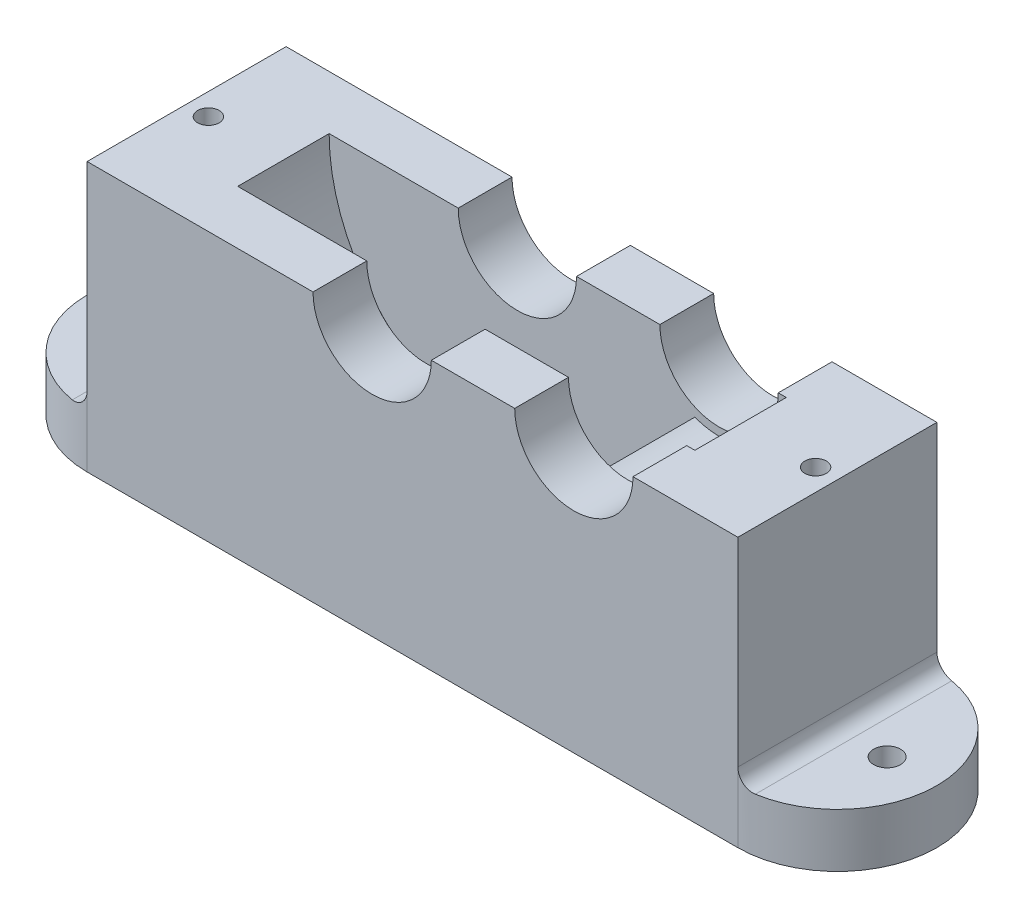
SolidWorks part; units mm, degrees
ref_plane "Front Plane" through (0, 0, 0) normal (0, 0, 1) x (1, 0, 0)
ref_plane "Top Plane" through (0, 0, 0) normal (0, 1, 0) x (1, 0, 0)
ref_plane "Right Plane" through (0, 0, 0) normal (1, 0, 0) x (0, 0, -1)
sketch "Sketch1" plane through (0, 0, 0) normal (0, 0, 1) x (1, 0, 0)
  line L0 (-18.75, 0) -> (18.75, 0)
  line L1 (-73.75, -5) -> (-73.75, -55)
  line L3 (-73.75, -5) -> (-73.75, 5)
  line L4 (-73.75, 5) -> (-63.4714, 5)
  line L10 (40.6874, 5) -> (51.25, 5)
  line L11 (51.25, -5) -> (51.25, 5)
  line L14 (51.25, -5) -> (51.25, -55)
  line L15 (51.25, -55) -> (-73.75, -55)
  circle A0 centre (18.75, 0) radius 7.5
  circle A1 centre (-18.75, 0) radius 30
  arc A2 (20.25, 22.4499) -> (20.25, -22.4499) centre (-18.75, 0) ccw
  arc A3 (20.25, -22.4499) -> (20.25, 22.4499) centre (18.75, 0) ccw
  circle A5 centre (18.75, 0) radius 22.5 construction
  circle A6 centre (-18.75, 0) radius 45 construction
  point P4 (0, 0)
  point P7 (-63.75, 0)
  point P10 (31.25, 0)
  point P13 (16.25, 0)
  point P19 (41.25, 0)
  dimension "D1" = 37.5
  dimension "D2" = 60
  dimension "D3" = 15
  dimension "D4" = 15
  dimension "D5" = 15
extrude "Boss-Extrude2" add sketch "Sketch1" along normal blind 27 contours A3 A2 A1 A0 | A1 | A0 region at (-27.6498, 42.6994, 0) region at (18.75, -7.2879, 0) region at (-47.9015, 0, 0)
shell "Shell5" thickness 10 removed face at (-11.25, 0, 0)
sketch "Sketch2" plane through (0, 0, 17) normal (0, 0, -1) x (-1, 0, 0)
  line L0 (-18.75, 0) -> (18.75, 0) construction
  circle A0 centre (-18.75, 0) radius 4
  circle A1 centre (18.75, 0) radius 4
  point P4 (0, 0)
sketch "Sketch4" plane through (0, 0, 0) normal (0, 0, -1) x (-1, 0, 0)
  arc A0 (-20.25, 22.4499) -> (-20.25, -22.4499) centre (-18.75, 0) ccw construction
  arc A1 (-20.25, -22.4499) -> (-20.25, 22.4499) centre (18.75, 0) ccw construction
  arc A4 (-20.25, 22.4499) -> (-20.25, -22.4499) centre (-18.75, 0) ccw
  arc A5 (-20.25, -22.4499) -> (-20.25, 22.4499) centre (18.75, 0) ccw
extrude "Boss-Extrude3" add sketch "Sketch4" along normal blind 10
sketch "Sketch5" plane through (0, 0, -10) normal (0, 0, -1) x (-1, 0, 0)
  line L0 (-18.75, 0) -> (18.75, 0) construction
  line L1 (-18.75, 0) -> (18.75, 0)
  circle A6 centre (-18.75, 0) radius 11
  circle A7 centre (18.75, 0) radius 11
extrude "Cut-Extrude2" cut sketch "Sketch5" against normal through all contours A6 | A7 region at (-18.75, 10.6889, -10) region at (29.4389, 0, -10)
sketch "Sketch8" plane through (0, 0, -10) normal (0, 0, -1) x (-1, 0, 0)
  line L0 (-41.25, 0) -> (63.75, 0) construction
  line L1 (11.25, 0) -> (11.25, 61.6014) construction
  line L2 (-41.25, 0) -> (-41.25, -50)
  line L3 (-41.25, -50) -> (63.75, -50)
  line L4 (63.75, -50) -> (63.75, 0)
  arc A0 (-20.25, 22.4499) -> (-20.25, -22.4499) centre (-18.75, 0) ccw construction
  arc A1 (-20.25, -22.4499) -> (-20.25, 22.4499) centre (18.75, 0) ccw construction
  arc A2 (-20.25, -22.4499) -> (63.75, 0) centre (18.75, 0) ccw
  arc A3 (-41.25, 0) -> (-20.25, -22.4499) centre (-18.75, 0) ccw
extrude "Boss-Extrude4" add sketch "Sketch8" against normal up to surface (37 mm away) up to face at (7.75, 0, 27)
sketch "Sketch9" plane through (0, 0, 0) normal (0, 1, 0) x (1, 0, 0)
  line L0 (-63.75, -8.5) -> (41.25, -8.5) construction
  line L5 (41.25, -27) -> (41.25, 10) construction
  line L6 (-11.25, -8.5) -> (-11.25, 40.864) construction
  line L11 (-63.75, -8.5) -> (-58.75, -8.5) construction
  line L12 (-58.75, -8.5) -> (-58.75, 10)
  line L13 (20.25, 10) -> (-63.75, 10) construction
  line L14 (-58.75, 10) -> (-71.75, 10)
  line L15 (-71.75, 10) -> (-71.75, -27)
  line L16 (-71.75, -27) -> (-58.75, -27)
  line L17 (-63.75, -27) -> (20.25, -27) construction
  line L18 (-58.75, -27) -> (-58.75, -8.5)
  line L19 (36.25, -27) -> (36.25, -8.5)
  line L20 (49.25, -27) -> (36.25, -27)
  line L21 (49.25, 10) -> (49.25, -27)
  line L22 (36.25, 10) -> (49.25, 10)
  line L23 (36.25, -8.5) -> (36.25, 10)
extrude "Boss-Extrude5" add sketch "Sketch9" along normal blind 3 and the other way up to surface (50 mm away) contours L16 L18 L12 L14 L15 | L23 L19 L20 L21 L22 region at (-65.25, 0, 8.5) region at (42.75, 0, 8.5) other way up to face at (-11.25, -50, 8.5)
sketch "Sketch10" plane through (0, 3, 0) normal (0, 1, 0) x (1, 0, 0)
  line L0 (-71.75, -8.5) -> (49.25, -8.5) construction
  line L1 (-71.75, 10) -> (-71.75, -27) construction
  line L2 (49.25, 10) -> (49.25, -27) construction
  line L3 (-11.25, -8.5) -> (-11.25, 28.9746) construction
  line L4 (-71.75, -8.5) -> (-63.6499, -8.5)
  line L5 (-63.6499, 10) -> (-63.6499, -27) construction
  circle A0 centre (-67.6999, -8.5) radius 2
  circle A1 centre (45.1999, -8.5) radius 2
extrude "Cut-Extrude3" cut sketch "Sketch10" against normal blind 10 contours A1 | A0
ref_plane "Plane1" through (0, 0, 0) normal (0, 1, 0) x (1, 0, 0)
sketch "Sketch11" plane through (0, 0, 0) normal (0, 1, 0) x (1, 0, 0)
  line L0 (49.25, -27) -> (41.0491, -27) construction
  line L1 (-71.75, 10) -> (49.25, 10)
  line L2 (-71.75, 10) -> (-71.75, -27)
  line L3 (-71.75, -27) -> (49.25, -27)
  line L4 (49.25, 10) -> (49.25, -27)
extrude "Cut-Extrude4" cut sketch "Sketch11" along normal through all
sketch "Sketch12" plane through (0, -50, 0) normal (0, -1, 0) x (1, 0, 0)
  line L0 (-71.75, 27) -> (49.25, 27)
  line L1 (-71.75, -10) -> (49.25, -10)
  arc A0 (49.25, 27) -> (49.25, -10) centre (49.25, 8.5) cw
  arc A1 (-71.75, 27) -> (-71.75, -10) centre (-71.75, 8.5) ccw
extrude "Boss-Extrude6" add sketch "Sketch12" against normal blind 10
fillet "Fillet1" radius 3 2 edges at (49.25, -40, 8.5) (-71.75, -40, 8.5)
sketch "Sketch13" plane through (0, -40, 0) normal (0, 1, 0) x (1, 0, 0)
  line L0 (-90.25, -8.5) -> (-71.75, -8.5) construction
  line L1 (-71.75, 10) -> (-71.75, -27) construction
  line L2 (67.75, -8.5) -> (49.25, -8.5) construction
  line L3 (49.25, -27) -> (49.25, 10) construction
  arc A0 (-74.75, 9.7551) -> (-74.75, -26.7551) centre (-71.75, -8.5) ccw construction
  arc A1 (52.25, -26.7551) -> (52.25, 9.7551) centre (49.25, -8.5) ccw construction
  circle A2 centre (-81, -8.5) radius 2.5
  circle A3 centre (58.5, -8.5) radius 2.5
extrude "Cut-Extrude5" cut sketch "Sketch13" against normal through all
